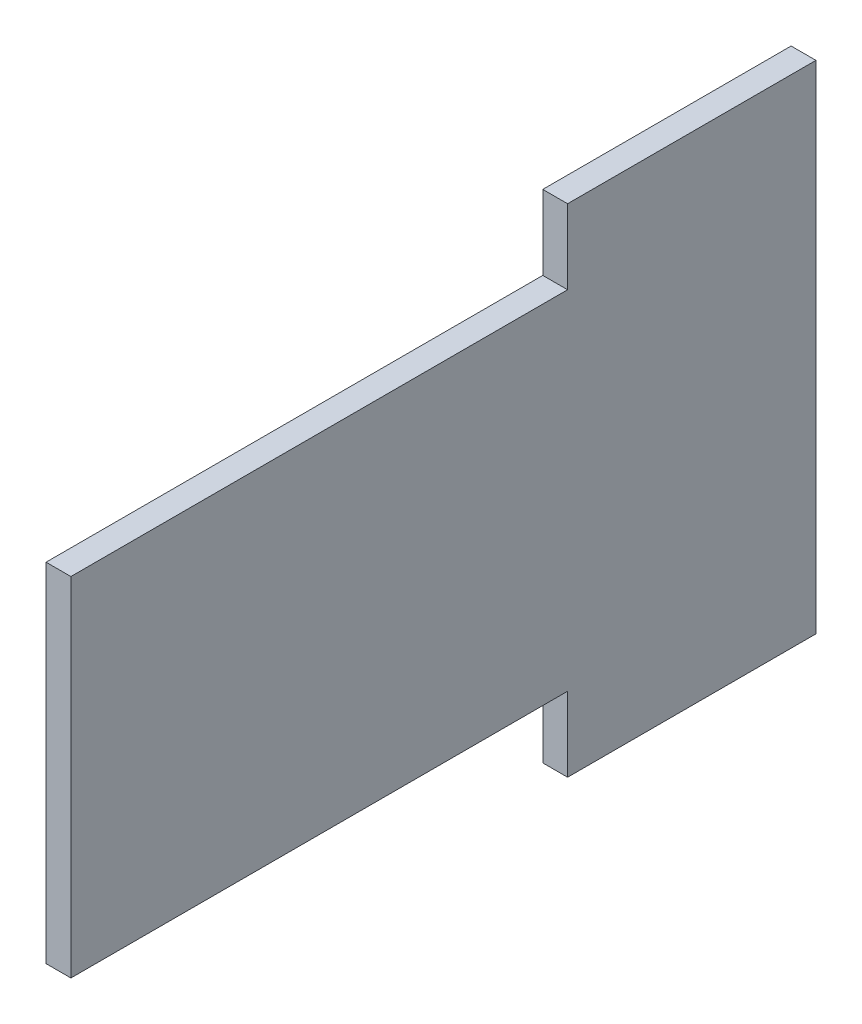
SolidWorks part; units mm, degrees
ref_plane "Front Plane" through (0, 0, 0) normal (1, 0, 0) x (0, 1, 0)
ref_plane "Top Plane" through (0, 0, 0) normal (0, 0, 1) x (0, 1, 0)
ref_plane "Right Plane" through (0, 0, 0) normal (0, 1, 0) x (-1, 0, 0)
sketch "Sketch1" plane through (0, 0, 0) normal (1, 0, 0) x (0, 1, 0)
  line L1 (50, 0) -> (50, 50)
  line L2 (50, 50) -> (35, 50)
  line L3 (35, 50) -> (35, 150)
  line L4 (35, 150) -> (-35, 150)
  line L5 (-35, 150) -> (-35, 50)
  line L6 (-35, 50) -> (-50, 50)
  line L7 (-50, 50) -> (-50, 0)
  line L8 (-50, 0) -> (0, 0)
  line L9 (0, 0) -> (50, 0)
  point P3 (50, 64.6282)
  dimension "D1" = 50
  dimension "D2" = 50
  dimension "D3" = 70
  dimension "D4" = 100
extrude "Boss-Extrude1" add sketch "Sketch1" along normal blind 5 contours L5 L6 L7 L8 L9 L1 L2 L3 L4
